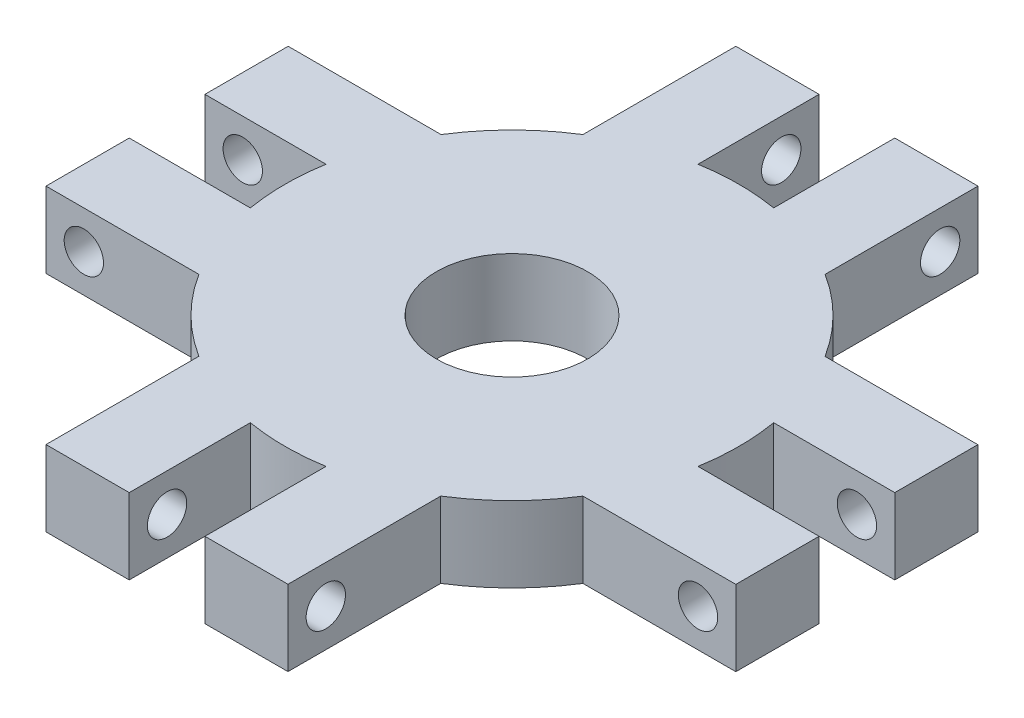
SolidWorks part; units mm, degrees
ref_plane "Front Plane" through (0, 0, 0) normal (0, 0, 1) x (1, 0, 0)
ref_plane "Top Plane" through (0, 0, 0) normal (0, 1, 0) x (1, 0, 0)
ref_plane "Right Plane" through (0, 0, 0) normal (1, 0, 0) x (0, 0, -1)
sketch "Sketch1" plane through (0, 0, 0) normal (0, 1, 0) x (1, 0, 0)
  line L0 (0, 19.05) -> (0, -19.05) construction
  line L1 (10.16, 19.05) -> (-10.16, 19.05) construction
  line L2 (3.175, 19.05) -> (-3.175, 19.05) construction
  line L3 (-3.175, 28.9436) -> (-10.16, 28.9436)
  line L4 (-3.175, 18.7836) -> (-3.175, 28.9436)
  line L5 (-10.16, 28.9436) -> (-10.16, 16.1145)
  line L6 (3.175, 18.7836) -> (3.175, 28.9436)
  line L7 (3.175, 28.9436) -> (10.16, 28.9436)
  line L8 (10.16, 28.9436) -> (10.16, 16.1145)
  line L9 (10.16, -19.05) -> (-10.16, -19.05) construction
  line L10 (3.175, -19.05) -> (-3.175, -19.05) construction
  line L11 (-3.175, -18.7836) -> (-3.175, -28.9436)
  line L12 (3.175, -18.7836) -> (3.175, -28.9436)
  line L13 (-3.175, -28.9436) -> (-10.16, -28.9436)
  line L14 (3.175, -28.9436) -> (10.1443, -28.9436)
  line L15 (-10.16, -28.9436) -> (-10.16, -16.1145)
  line L16 (10.1443, -28.9436) -> (10.1443, -16.1244)
  line L17 (-19.05, 0) -> (19.05, 0) construction
  line L18 (-19.05, 10.16) -> (-19.05, -10.16) construction
  line L19 (-19.05, 3.175) -> (-19.05, -3.175) construction
  line L20 (-18.7836, -3.175) -> (-28.9436, -3.175)
  line L21 (-18.7836, 3.175) -> (-28.9436, 3.175)
  line L22 (-28.9436, 3.175) -> (-28.9436, 10.16)
  line L23 (-28.9436, -3.175) -> (-28.9436, -10.16)
  line L24 (-28.9436, -10.16) -> (-16.1145, -10.16)
  line L25 (-28.9436, 10.16) -> (-16.1145, 10.16)
  line L26 (19.05, 10.16) -> (19.05, -10.16) construction
  line L27 (19.05, -3.175) -> (19.05, 3.175) construction
  line L28 (18.7836, 3.175) -> (28.9436, 3.175)
  line L29 (18.7836, -3.175) -> (28.9436, -3.175)
  line L30 (28.9436, -3.175) -> (28.9436, -10.16)
  line L31 (28.9436, 3.175) -> (28.9436, 10.1466)
  line L32 (28.9436, 10.1466) -> (16.1229, 10.1466)
  line L33 (28.9436, -10.16) -> (16.1145, -10.16)
  circle A0 centre (0, 0) radius 19.05
  point P7 (0, 19.05)
  point P8 (0, 19.05)
  point P10 (0, 19.05)
  point P14 (0, 19.05)
  point P24 (0, -19.05)
  point P26 (0, -19.05)
  point P40 (-19.05, 0)
  point P42 (-19.05, 0)
  point P54 (19.05, 0)
  point P56 (19.05, 0)
extrude "Boss-Extrude1" add sketch "Sketch1" along normal blind 6.35 contours A0 L4 L3 L5 | A0 L8 L7 L6 | A0 L25 L22 L21 | A0 L20 L23 L24 | A0 L15 L13 L11 | A0 L12 L14 L16 | A0 L33 L30 L29 | A0 L28 L31 L32 | A0 region at (-6.8046, 0, -23.3022) region at (6.8046, 0, -23.3022) region at (-23.3022, 0, -6.8046) region at (23.3039, 0, -6.7973) region at (-23.3022, 0, 6.8046) region at (-6.8046, 0, 23.3022) region at (23.3022, 0, 6.8046) region at (6.796, 0, 23.3042)
sketch "Sketch2" plane through (10.16, 0, 0) normal (1, 0, 0) x (0, 0, -1)
  line L0 (28.9436, 3.175) -> (25.7686, 3.175) construction
  line L1 (28.9436, 6.35) -> (28.9436, 0) construction
  circle A0 centre (25.7686, 3.175) radius 1.651
extrude "Cut-Extrude1" cut sketch "Sketch2" against normal blind 23.368
sketch "Sketch3" plane through (0, 0, -10.1466) normal (0, 0, -1) x (-1, 0, 0)
  line L0 (-28.9436, 3.175) -> (-25.7686, 3.175) construction
  line L1 (-28.9436, 6.35) -> (-28.9436, 0) construction
  circle A0 centre (-25.7686, 3.175) radius 1.651
extrude "Cut-Extrude2" cut sketch "Sketch3" against normal blind 23.368
sketch "Sketch4" plane through (10.1443, 0, 0) normal (1, 0, 0) x (0, 0, -1)
  line L0 (-28.9436, 3.175) -> (-25.7686, 3.175) construction
  line L1 (-28.9436, 6.35) -> (-28.9436, 0) construction
  circle A0 centre (-25.7686, 3.175) radius 1.651
extrude "Cut-Extrude3" cut sketch "Sketch4" against normal blind 23.368
sketch "Sketch5" plane through (0, 0, 10.16) normal (0, 0, 1) x (1, 0, 0)
  line L0 (-28.9436, 3.175) -> (-25.7686, 3.175) construction
  line L1 (-28.9436, 6.35) -> (-28.9436, 0) construction
  circle A0 centre (-25.7686, 3.175) radius 1.651
extrude "Cut-Extrude4" cut sketch "Sketch5" against normal blind 23.368
sketch "Sketch6" plane through (0, 6.35, 0) normal (0, 1, 0) x (1, 0, 0)
  circle A0 centre (0, 0) radius 6.35
extrude "Cut-Extrude5" cut sketch "Sketch6" against normal blind 14.3002
